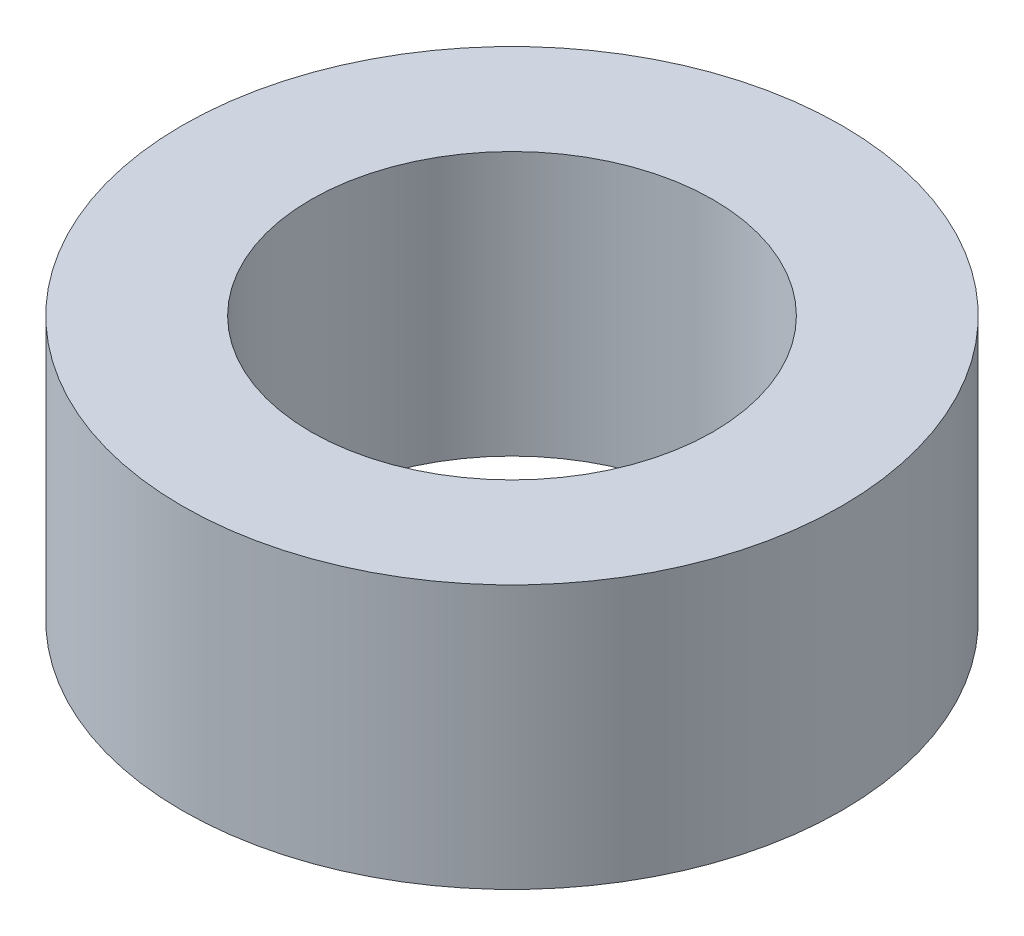
SolidWorks part; units mm, degrees
ref_plane "Front Plane" through (0, 0, 0) normal (0, 0, 1) x (1, 0, 0)
ref_plane "Top Plane" through (0, 0, 0) normal (0, 1, 0) x (1, 0, 0)
ref_plane "Right Plane" through (0, 0, 0) normal (1, 0, 0) x (0, 0, -1)
sketch "Sketch1" plane through (0, 0, 0) normal (0, 1, 0) x (1, 0, 0)
  circle A0 centre (0, 0) radius 3.05
  circle A1 centre (0, 0) radius 5
  dimension "D1" = 6.1
  dimension "D2" = 10
extrude "Boss-Extrude1" add sketch "Sketch1" along normal mid plane 4
